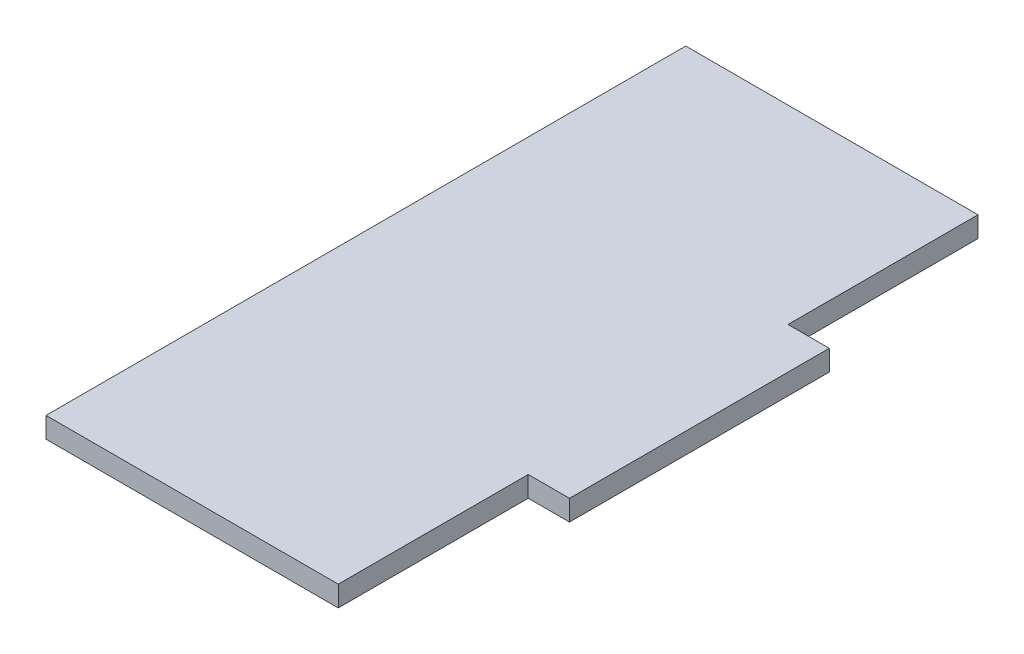
SolidWorks part; units mm, degrees
material "Cedar"
ref_plane "Front Plane" through (0, 0, 0) normal (0, 0, 1) x (1, 0, 0)
ref_plane "Top Plane" through (0, 0, 0) normal (0, 1, 0) x (1, 0, 0)
ref_plane "Right Plane" through (0, 0, 0) normal (1, 0, 0) x (0, 0, -1)
sketch "Sketch1" plane through (0, 0, 0) normal (0, 1, 0) x (1, 0, 0)
  line L0 (-22.5, 29.25) -> (22.5, 29.25)
  line L1 (22.5, 29.25) -> (22.5, 0)
  line L2 (22.5, 0) -> (28.85, 0)
  line L3 (28.85, 0) -> (28.85, -40)
  line L4 (28.85, -40) -> (22.5, -40)
  line L5 (22.5, -40) -> (22.5, -69.25)
  line L6 (22.5, -69.25) -> (-22.5, -69.25)
  line L7 (-22.5, -69.25) -> (-22.5, -40)
  line L8 (-22.5, -40) -> (-28.85, -40)
  line L9 (-28.85, -40) -> (-28.85, 0)
  line L10 (-28.85, 0) -> (-22.5, 0)
  line L11 (-22.5, 0) -> (-22.5, 29.25)
  line L12 (-22.5, 0) -> (-22.5, -40) construction
  point P11 (0, 29.25)
  point P14 (-28.85, -20)
  dimension "D1" = 6.35
  dimension "D2" = 40
  dimension "D3" = 45
  dimension "D4" = 98.5
extrude "Boss-Extrude1" add sketch "Sketch1" along normal blind 3.175 contours L11 L12 L7 L6 L5 L4 L3 L2 L1 L0 region at (1.3915, 0, 20)
equation "\"length\"= 98.5mm"
equation "\"w_mach\"= 45mm"
equation "\"w_tab\"= 40mm"
equation "\"t_wood\"= 0.125in"
equation "\"t_side\"= 0.25in"
equation "\"D1@Sketch1\"=\"t_side\""
equation "\"D2@Sketch1\"=\"w_tab\""
equation "\"D3@Sketch1\"=\"w_mach\""
equation "\"D4@Sketch1\"=\"length\""
equation "\"D1@Boss-Extrude1\"=\"t_wood\""
